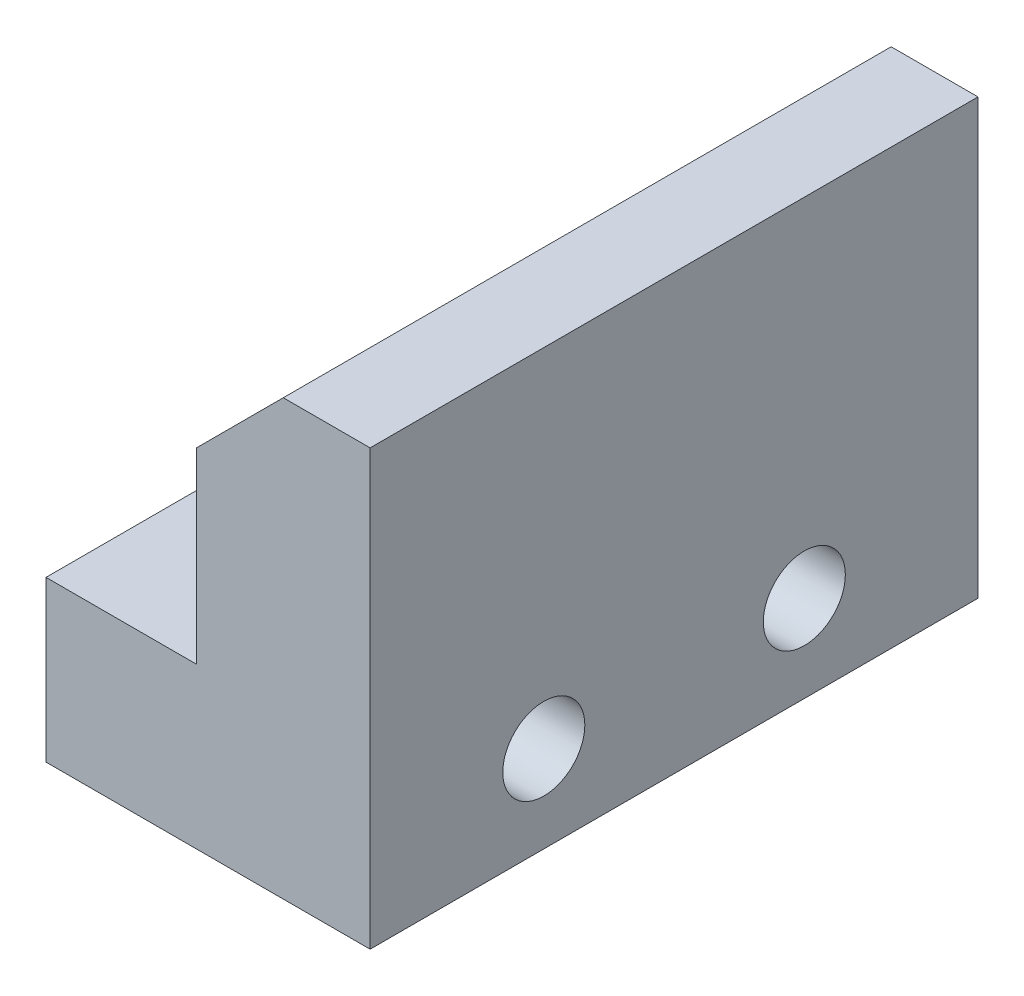
SolidWorks part; units mm, degrees
material "PETG"
ref_plane "Front Plane" through (0, 0, 0) normal (0, 0, 1) x (1, 0, 0)
ref_plane "Top Plane" through (0, 0, 0) normal (0, 1, 0) x (1, 0, 0)
ref_plane "Right Plane" through (0, 0, 0) normal (1, 0, 0) x (0, 0, -1)
sketch "Sketch1" plane through (0, 0, 0) normal (0, 0, 1) x (1, 0, 0)
  line L0 (47.4, 63.5) -> (22, 38.1)
  line L1 (0, -12.7) -> (47.4, -12.7)
  line L2 (0, -12.7) -> (0, 12.7)
  line L3 (0, 12.7) -> (22, 12.7)
  line L5 (22, 63.5) -> (47.4, 63.5)
  line L6 (22, 63.5) -> (22, 12.7)
  line L8 (47.4, 63.5) -> (47.4, -12.7)
  line L9 (34.7, 50.8) -> (47.4, 50.8)
  line L10 (0, 10.7) -> (22, 10.7)
  line L11 (22, 10.7) -> (22, 12.7)
  dimension "D1" = 25.4
  dimension "D2" = 47.4
  dimension "D3" = 25.4
  dimension "D4" = 50.8
  dimension "D5" = 25.4
  dimension "D6" = 12.7
  dimension "D7" = 2
extrude "Boss-Extrude1" add sketch "Sketch1" along normal mid plane 88.9 contours L8 L0 L6 L3 L2 L1 region at (29.0734, 12.9237, 0)
sketch "Sketch2" plane through (47.4, 0, 0) normal (1, 0, 0) x (0, 0, -1)
  line L0 (-19.05, 0) -> (0, 0) construction
  line L1 (0, 0) -> (19.05, 0) construction
  line L2 (-44.45, 50.8) -> (-44.45, -12.7) construction
  circle A0 centre (-19.05, 0) radius 3.25
  circle A1 centre (19.05, 0) radius 3.25
  dimension "D1" = 6.5
  dimension "D2" = 25.4
extrude "Cut-Extrude1" cut sketch "Sketch2" against normal through all
sketch "Sketch3" plane through (47.4, 0, 0) normal (1, 0, 0) x (0, 0, -1)
  circle A0 centre (-19.05, 0) radius 6
  circle A1 centre (19.05, 0) radius 6
  dimension "D1" = 12
extrude "Cut-Extrude2" cut sketch "Sketch3" against normal offset from surface (37.4 mm away) 10 up to face at (0, 0, 15.8)
equation "\"D2@Sketch1\"   = 22mm + 1in"
